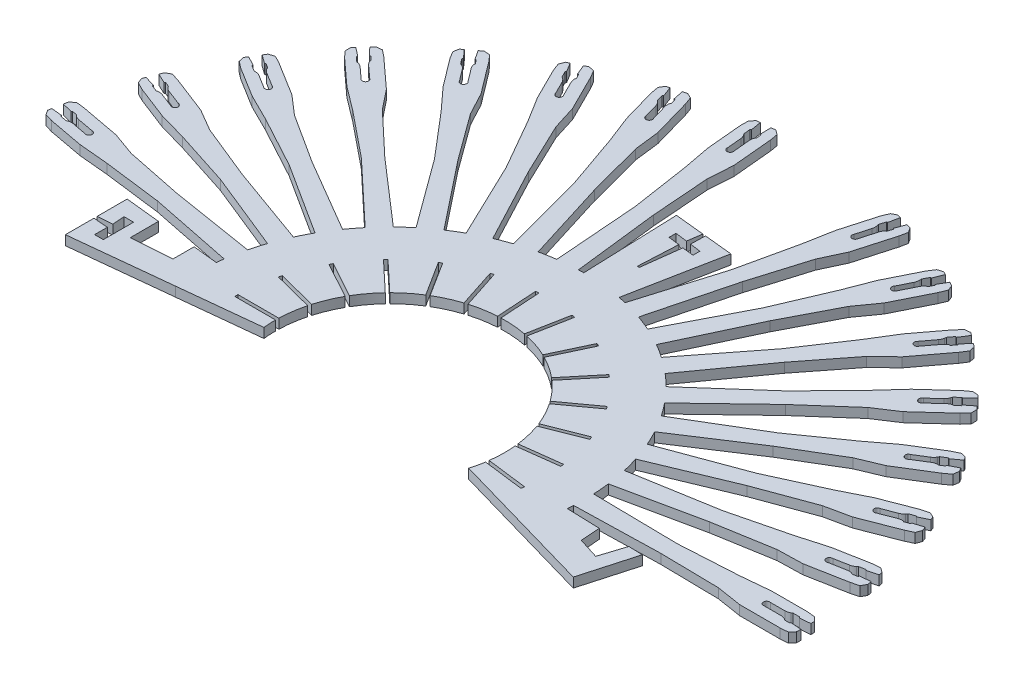
SolidWorks part; units mm, degrees
ref_plane "Front Plane" through (0, 0, 0) normal (0, 0, 1) x (1, 0, 0)
ref_plane "Top Plane" through (0, 0, 0) normal (0, 1, 0) x (1, 0, 0)
ref_plane "Right Plane" through (0, 0, 0) normal (1, 0, 0) x (0, 0, -1)
sketch "Sketch1" plane through (0, 0, 0) normal (0, 1, 0) x (1, 0, 0)
  line L5558 (72.849, 49.9) -> (72.743, 47.748) construction
  line L5559 (72.743, 47.748) -> (72.425, 45.667) construction
  line L5560 (72.425, 45.667) -> (71.896, 43.656) construction
  line L5561 (71.896, 43.656) -> (71.208, 41.716) construction
  line L5562 (71.208, 41.716) -> (70.309, 39.899) construction
  line L5563 (70.309, 39.899) -> (69.286, 38.171) construction
  line L5564 (69.286, 38.171) -> (66.71, 35.048) construction
  line L5565 (66.71, 35.048) -> (63.588, 32.491) construction
  line L5566 (63.588, 32.491) -> (61.877, 31.45) construction
  line L5567 (61.877, 31.45) -> (60.043, 30.551) construction
  line L5568 (60.043, 30.551) -> (58.12, 29.863) construction
  line L5569 (58.12, 29.863) -> (56.109, 29.333) construction
  line L5570 (56.109, 29.333) -> (54.01, 29.016) construction
  line L5571 (54.01, 29.016) -> (51.876, 28.91) construction
  line L5572 (51.876, 28.91) -> (49.724, 29.016) construction
  line L5573 (49.724, 29.016) -> (47.643, 29.333) construction
  line L5574 (47.643, 29.333) -> (45.632, 29.863) construction
  line L5575 (45.632, 29.863) -> (43.692, 30.551) construction
  line L5576 (43.692, 30.551) -> (41.839, 31.45) construction
  line L5577 (41.839, 31.45) -> (40.128, 32.491) construction
  line L5578 (40.128, 32.491) -> (37.006, 35.048) construction
  line L5579 (37.006, 35.048) -> (34.431, 38.171) construction
  line L5580 (34.431, 38.171) -> (33.408, 39.899) construction
  line L5581 (33.408, 39.899) -> (32.508, 41.716) construction
  line L5582 (32.508, 41.716) -> (31.821, 43.656) construction
  line L5583 (31.821, 43.656) -> (31.291, 45.667) construction
  line L5584 (31.291, 45.667) -> (30.974, 47.748) construction
  line L5585 (30.974, 47.748) -> (30.868, 49.9) construction
  line L5586 (30.868, 49.9) -> (30.974, 52.035) construction
  line L5587 (30.974, 52.035) -> (31.291, 54.134) construction
  line L5588 (31.291, 54.134) -> (31.821, 56.145) construction
  line L5589 (31.821, 56.145) -> (32.508, 58.067) construction
  line L5590 (32.508, 58.067) -> (33.408, 59.919) construction
  line L5591 (33.408, 59.919) -> (34.431, 61.648) construction
  line L5592 (34.431, 61.648) -> (37.006, 64.77) construction
  line L5593 (37.006, 64.77) -> (40.128, 67.328) construction
  line L5594 (40.128, 67.328) -> (41.839, 68.368) construction
  line L5595 (41.839, 68.368) -> (43.692, 69.268) construction
  line L5596 (43.692, 69.268) -> (45.632, 69.956) construction
  line L5597 (45.632, 69.956) -> (47.643, 70.485) construction
  line L5598 (47.643, 70.485) -> (49.724, 70.803) construction
  line L5599 (49.724, 70.803) -> (51.876, 70.908) construction
  line L5600 (51.876, 70.908) -> (54.01, 70.803) construction
  line L5601 (54.01, 70.803) -> (56.109, 70.485) construction
  line L5602 (56.109, 70.485) -> (58.12, 69.956) construction
  line L5603 (58.12, 69.956) -> (60.043, 69.268) construction
  line L5604 (60.043, 69.268) -> (61.877, 68.368) construction
  line L5605 (61.877, 68.368) -> (63.588, 67.328) construction
  line L5606 (63.588, 67.328) -> (66.71, 64.77) construction
  line L5607 (66.71, 64.77) -> (69.286, 61.648) construction
  line L5608 (69.286, 61.648) -> (70.309, 59.919) construction
  line L5609 (70.309, 59.919) -> (71.208, 58.067) construction
  line L5610 (71.208, 58.067) -> (71.896, 56.145) construction
  line L5611 (71.896, 56.145) -> (72.425, 54.134) construction
  line L5612 (72.425, 54.134) -> (72.743, 52.035) construction
  line L5613 (72.743, 52.035) -> (72.849, 49.9) construction
  line L5614 (62.054, 49.9) -> (61.842, 47.854) construction
  line L5615 (61.842, 47.854) -> (61.26, 45.932) construction
  line L5616 (61.26, 45.932) -> (60.307, 44.203) construction
  line L5617 (60.307, 44.203) -> (59.055, 42.704) construction
  line L5618 (59.055, 42.704) -> (57.556, 41.451) construction
  line L5619 (57.556, 41.451) -> (55.827, 40.499) construction
  line L5620 (55.827, 40.499) -> (53.922, 39.917) construction
  line L5621 (53.922, 39.917) -> (51.858, 39.705) construction
  line L5622 (51.858, 39.705) -> (49.795, 39.917) construction
  line L5623 (49.795, 39.917) -> (47.89, 40.499) construction
  line L5624 (47.89, 40.499) -> (46.143, 41.451) construction
  line L5625 (46.143, 41.451) -> (44.644, 42.704) construction
  line L5626 (44.644, 42.704) -> (43.392, 44.203) construction
  line L5627 (43.392, 44.203) -> (42.439, 45.932) construction
  line L5628 (42.439, 45.932) -> (41.857, 47.854) construction
  line L5629 (41.857, 47.854) -> (41.645, 49.9) construction
  line L5630 (41.645, 49.9) -> (41.857, 51.964) construction
  line L5631 (41.857, 51.964) -> (42.439, 53.869) construction
  line L5632 (42.439, 53.869) -> (43.392, 55.615) construction
  line L5633 (43.392, 55.615) -> (44.644, 57.115) construction
  line L5634 (44.644, 57.115) -> (46.143, 58.367) construction
  line L5635 (46.143, 58.367) -> (47.89, 59.32) construction
  line L5636 (47.89, 59.32) -> (49.795, 59.902) construction
  line L5637 (49.795, 59.902) -> (51.858, 60.113) construction
  line L5638 (51.858, 60.113) -> (53.922, 59.902) construction
  line L5639 (53.922, 59.902) -> (55.827, 59.32) construction
  line L5640 (55.827, 59.32) -> (57.556, 58.367) construction
  line L5641 (57.556, 58.367) -> (59.055, 57.115) construction
  line L5642 (59.055, 57.115) -> (60.307, 55.615) construction
  line L5643 (60.307, 55.615) -> (61.26, 53.869) construction
  line L5644 (61.26, 53.869) -> (61.842, 51.964) construction
  line L5645 (61.842, 51.964) -> (62.054, 49.9) construction
  line L5646 (30.85, 49.9) -> (51.841, 49.9) construction
  line L5647 (53.675, 70.82) -> (51.841, 49.9) construction
  line L5648 (72.531, 46.249) -> (51.858, 49.9) construction
  line L5649 (72.796, 48.436) -> (51.841, 49.9) construction
  line L5650 (51.488, 70.891) -> (51.841, 49.9) construction
  line L5651 (55.862, 70.52) -> (51.858, 49.9) construction
  line L5652 (30.956, 47.696) -> (51.841, 49.9) construction
  line L5653 (30.956, 52.088) -> (51.841, 49.9) construction
  line L5654 (72.037, 44.115) -> (51.841, 49.9) construction
  line L5655 (62.406, 49.177) -> (67.045, 49.424) construction
  line L5656 (67.345, 50.077) -> (67.469, 50.324) construction
  line L5657 (67.469, 50.324) -> (67.68, 50.377) construction
  line L5658 (67.68, 50.377) -> (67.892, 50.271) construction
  line L5659 (67.892, 50.271) -> (67.945, 50.059) construction
  line L5660 (67.945, 50.059) -> (67.839, 49.848) construction
  line L5661 (67.839, 49.848) -> (67.628, 49.759) construction
  line L5662 (67.628, 49.759) -> (67.416, 49.865) construction
  line L5663 (67.416, 49.865) -> (67.345, 50.077) construction
  line L5664 (69.832, 50.094) -> (69.938, 50.341) construction
  line L5665 (69.938, 50.341) -> (70.168, 50.394) construction
  line L5666 (70.168, 50.394) -> (70.379, 50.288) construction
  line L5667 (70.379, 50.288) -> (70.432, 50.077) construction
  line L5668 (70.432, 50.077) -> (70.326, 49.865) construction
  line L5669 (70.326, 49.865) -> (70.115, 49.777) construction
  line L5670 (70.115, 49.777) -> (69.903, 49.883) construction
  line L5671 (69.903, 49.883) -> (69.832, 50.094) construction
  line L5672 (67.045, 49.424) -> (71.702, 49.477) construction
  line L5673 (71.914, 50.094) -> (71.702, 49.477) construction
  line L5674 (62.389, 50.835) -> (67.045, 50.659) construction
  line L5675 (67.045, 50.659) -> (71.702, 50.712) construction
  line L5676 (71.914, 50.094) -> (71.702, 50.712) construction
  line L5677 (70.132, 50.377) -> (67.645, 50.359) construction
  line L5678 (70.15, 49.777) -> (67.645, 49.742) construction
  line L5679 (57.344, 49.953) -> (51.841, 49.9) construction
  line L5680 (62.353, 51.118) -> (66.887, 52.229) construction
  line L5681 (67.045, 52.917) -> (67.345, 53.252) construction
  line L5682 (67.345, 53.252) -> (67.557, 53.199) construction
  line L5683 (67.557, 53.199) -> (67.663, 52.987) construction
  line L5684 (67.663, 52.987) -> (67.61, 52.776) construction
  line L5685 (67.61, 52.776) -> (67.398, 52.652) construction
  line L5686 (67.398, 52.652) -> (67.187, 52.723) construction
  line L5687 (67.187, 52.723) -> (67.045, 52.917) construction
  line L5688 (69.48, 53.393) -> (69.779, 53.746) construction
  line L5689 (69.779, 53.746) -> (69.991, 53.693) construction
  line L5690 (69.991, 53.693) -> (70.097, 53.481) construction
  line L5691 (70.097, 53.481) -> (70.044, 53.269) construction
  line L5692 (70.044, 53.269) -> (69.832, 53.128) construction
  line L5693 (69.832, 53.128) -> (69.621, 53.217) construction
  line L5694 (69.621, 53.217) -> (69.48, 53.393) construction
  line L5695 (66.887, 52.229) -> (71.455, 53.128) construction
  line L5696 (71.543, 53.763) -> (71.455, 53.128) construction
  line L5697 (62.036, 52.758) -> (66.64, 53.428) construction
  line L5698 (66.64, 53.428) -> (71.208, 54.328) construction
  line L5699 (71.543, 53.781) -> (71.208, 54.328) construction
  line L5700 (69.744, 53.728) -> (67.292, 53.252) construction
  line L5701 (69.85, 53.128) -> (67.416, 52.634) construction
  line L5702 (57.238, 50.959) -> (51.841, 49.9) construction
  line L5703 (61.965, 53.023) -> (66.199, 54.945) construction
  line L5704 (66.234, 55.651) -> (66.446, 56.039) construction
  line L5705 (66.446, 56.039) -> (66.693, 56.021) construction
  line L5706 (66.693, 56.021) -> (66.851, 55.827) construction
  line L5707 (66.851, 55.827) -> (66.64, 55.457) construction
  line L5708 (66.64, 55.457) -> (66.393, 55.492) construction
  line L5709 (66.393, 55.492) -> (66.234, 55.651) construction
  line L5710 (68.545, 56.568) -> (68.756, 56.956) construction
  line L5711 (68.756, 56.956) -> (69.003, 56.938) construction
  line L5712 (69.003, 56.938) -> (69.162, 56.744) construction
  line L5713 (69.162, 56.744) -> (68.95, 56.374) construction
  line L5714 (68.95, 56.374) -> (68.703, 56.409) construction
  line L5715 (68.703, 56.409) -> (68.545, 56.568) construction
  line L5716 (66.199, 54.945) -> (70.52, 56.656) construction
  line L5717 (70.503, 57.309) -> (70.52, 56.656) construction
  line L5718 (61.348, 54.575) -> (65.74, 56.092) construction
  line L5719 (65.74, 56.092) -> (70.079, 57.803) construction
  line L5720 (70.503, 57.309) -> (70.079, 57.803) construction
  line L5721 (68.739, 56.938) -> (66.41, 56.021) construction
  line L5722 (68.968, 56.374) -> (66.64, 55.439) construction
  line L5723 (56.956, 51.929) -> (51.841, 49.9) construction
  line L5724 (61.225, 54.822) -> (65.035, 57.485) construction
  line L5725 (64.946, 58.191) -> (65.07, 58.614) construction
  line L5726 (65.07, 58.614) -> (65.317, 58.632) construction
  line L5727 (65.317, 58.632) -> (65.493, 58.473) construction
  line L5728 (65.493, 58.473) -> (65.528, 58.244) construction
  line L5729 (65.528, 58.244) -> (65.37, 58.05) construction
  line L5730 (65.37, 58.05) -> (64.946, 58.191) construction
  line L5731 (67.045, 59.514) -> (67.169, 59.937) construction
  line L5732 (67.169, 59.937) -> (67.416, 59.955) construction
  line L5733 (67.416, 59.955) -> (67.592, 59.796) construction
  line L5734 (67.592, 59.796) -> (67.628, 59.567) construction
  line L5735 (67.628, 59.567) -> (67.469, 59.373) construction
  line L5736 (67.469, 59.373) -> (67.045, 59.514) construction
  line L5737 (65.035, 57.485) -> (68.968, 59.972) construction
  line L5738 (68.827, 60.607) -> (68.968, 59.972) construction
  line L5739 (60.325, 56.233) -> (64.382, 58.526) construction
  line L5740 (64.382, 58.526) -> (68.315, 61.013) construction
  line L5741 (68.827, 60.607) -> (68.315, 61.013) construction
  line L5742 (67.169, 59.919) -> (65.052, 58.579) construction
  line L5743 (67.486, 59.39) -> (65.37, 58.067) construction
  line L5744 (56.497, 52.828) -> (51.858, 49.9) construction
  line L5745 (60.149, 56.444) -> (63.429, 59.761) construction
  line L5746 (63.2, 60.448) -> (63.147, 60.678) construction
  line L5747 (63.147, 60.678) -> (63.288, 60.889) construction
  line L5748 (63.288, 60.889) -> (63.5, 60.942) construction
  line L5749 (63.5, 60.942) -> (63.712, 60.837) construction
  line L5750 (63.712, 60.837) -> (63.765, 60.607) construction
  line L5751 (63.765, 60.607) -> (63.659, 60.396) construction
  line L5752 (63.659, 60.396) -> (63.412, 60.343) construction
  line L5753 (63.412, 60.343) -> (63.2, 60.448) construction
  line L5754 (65.017, 62.124) -> (64.964, 62.371) construction
  line L5755 (64.964, 62.371) -> (65.105, 62.583) construction
  line L5756 (65.105, 62.583) -> (65.317, 62.636) construction
  line L5757 (65.317, 62.636) -> (65.528, 62.53) construction
  line L5758 (65.528, 62.53) -> (65.581, 62.283) construction
  line L5759 (65.581, 62.283) -> (65.476, 62.071) construction
  line L5760 (65.476, 62.071) -> (65.229, 62.018) construction
  line L5761 (65.229, 62.018) -> (65.017, 62.124) construction
  line L5762 (63.429, 59.761) -> (66.834, 62.936) construction
  line L5763 (66.587, 63.535) -> (66.834, 62.936) construction
  line L5764 (59.02, 57.679) -> (62.583, 60.678) construction
  line L5765 (62.583, 60.678) -> (66.005, 63.835) construction
  line L5766 (66.587, 63.535) -> (66.005, 63.835) construction
  line L5767 (65.07, 62.548) -> (63.235, 60.854) construction
  line L5768 (65.493, 62.089) -> (63.659, 60.396) construction
  line L5769 (55.88, 53.622) -> (51.841, 49.9) construction
  line L5770 (58.808, 57.873) -> (61.419, 61.718) construction
  line L5771 (61.083, 62.353) -> (60.995, 62.583) construction
  line L5772 (60.995, 62.583) -> (61.083, 62.794) construction
  line L5773 (61.083, 62.794) -> (61.295, 62.9) construction
  line L5774 (61.295, 62.9) -> (61.507, 62.83) construction
  line L5775 (61.507, 62.83) -> (61.613, 62.618) construction
  line L5776 (61.613, 62.618) -> (61.524, 62.371) construction
  line L5777 (61.524, 62.371) -> (61.313, 62.301) construction
  line L5778 (61.313, 62.301) -> (61.083, 62.353) construction
  line L5779 (62.565, 64.329) -> (62.477, 64.576) construction
  line L5780 (62.477, 64.576) -> (62.565, 64.788) construction
  line L5781 (62.565, 64.788) -> (62.777, 64.893) construction
  line L5782 (62.777, 64.893) -> (62.988, 64.805) construction
  line L5783 (62.988, 64.805) -> (63.094, 64.594) construction
  line L5784 (63.094, 64.594) -> (63.006, 64.364) construction
  line L5785 (63.006, 64.364) -> (62.794, 64.276) construction
  line L5786 (62.794, 64.276) -> (62.565, 64.329) construction
  line L5787 (61.419, 61.718) -> (64.206, 65.458) construction
  line L5788 (63.835, 66.005) -> (64.206, 65.458) construction
  line L5789 (57.485, 58.861) -> (60.431, 62.459) construction
  line L5790 (60.431, 62.459) -> (63.2, 66.199) construction
  line L5791 (63.835, 66.005) -> (63.2, 66.199) construction
  line L5792 (62.53, 64.752) -> (61.031, 62.759) construction
  line L5793 (63.024, 64.382) -> (61.524, 62.389) construction
  line L5794 (55.122, 54.31) -> (51.858, 49.9) construction
  line L5795 (57.238, 59.002) -> (59.09, 63.271) construction
  line L5796 (58.649, 63.835) -> (58.508, 64.047) construction
  line L5797 (58.508, 64.047) -> (58.561, 64.258) construction
  line L5798 (58.561, 64.258) -> (58.755, 64.417) construction
  line L5799 (58.755, 64.417) -> (58.967, 64.364) construction
  line L5800 (58.967, 64.364) -> (59.126, 64.17) construction
  line L5801 (59.126, 64.17) -> (59.073, 63.941) construction
  line L5802 (59.073, 63.941) -> (58.879, 63.8) construction
  line L5803 (58.879, 63.8) -> (58.649, 63.835) construction
  line L5804 (59.743, 66.058) -> (59.602, 66.269) construction
  line L5805 (59.602, 66.269) -> (59.655, 66.481) construction
  line L5806 (59.655, 66.481) -> (59.849, 66.604) construction
  line L5807 (59.849, 66.604) -> (60.06, 66.587) construction
  line L5808 (60.06, 66.587) -> (60.219, 66.393) construction
  line L5809 (60.219, 66.393) -> (60.166, 66.163) construction
  line L5810 (60.166, 66.163) -> (59.972, 66.022) construction
  line L5811 (59.972, 66.022) -> (59.743, 66.058) construction
  line L5812 (59.09, 63.271) -> (61.136, 67.451) construction
  line L5813 (60.695, 67.927) -> (61.136, 67.451) construction
  line L5814 (55.739, 59.743) -> (57.979, 63.818) construction
  line L5815 (57.979, 63.818) -> (60.025, 67.998) construction
  line L5816 (60.678, 67.927) -> (60.025, 67.998) construction
  line L5817 (59.619, 66.463) -> (58.526, 64.223) construction
  line L5818 (60.184, 66.181) -> (59.073, 63.941) construction
  line L5819 (54.257, 54.822) -> (51.841, 49.9) construction
  line L5820 (55.457, 59.849) -> (56.497, 64.382) construction
  line L5821 (55.951, 64.841) -> (55.792, 64.999) construction
  line L5822 (55.792, 64.999) -> (55.792, 65.246) construction
  line L5823 (55.792, 65.246) -> (55.951, 65.423) construction
  line L5824 (55.951, 65.423) -> (56.18, 65.423) construction
  line L5825 (56.18, 65.423) -> (56.339, 65.264) construction
  line L5826 (56.339, 65.264) -> (56.339, 65.035) construction
  line L5827 (56.339, 65.035) -> (56.18, 64.876) construction
  line L5828 (56.18, 64.876) -> (55.951, 64.841) construction
  line L5829 (56.603, 67.239) -> (56.444, 67.398) construction
  line L5830 (56.444, 67.398) -> (56.444, 67.628) construction
  line L5831 (56.444, 67.628) -> (56.603, 67.822) construction
  line L5832 (56.603, 67.822) -> (56.85, 67.822) construction
  line L5833 (56.85, 67.822) -> (57.009, 67.663) construction
  line L5834 (57.009, 67.663) -> (57.009, 67.416) construction
  line L5835 (57.009, 67.416) -> (56.85, 67.257) construction
  line L5836 (56.85, 67.257) -> (56.603, 67.239) construction
  line L5837 (56.497, 64.382) -> (57.732, 68.88) construction
  line L5838 (57.203, 69.25) -> (57.732, 68.88) construction
  line L5839 (53.852, 60.29) -> (55.298, 64.717) construction
  line L5840 (55.298, 64.717) -> (56.533, 69.197) construction
  line L5841 (57.185, 69.25) -> (56.533, 69.197) construction
  line L5842 (56.427, 67.61) -> (55.757, 65.211) construction
  line L5843 (57.009, 67.451) -> (56.356, 65.035) construction
  line L5844 (53.305, 55.192) -> (51.841, 49.9) construction
  line L5845 (51.664, 60.484) -> (50.994, 65.088) construction
  line L5846 (50.324, 65.317) -> (50.112, 65.423) construction
  line L5847 (50.112, 65.423) -> (50.024, 65.634) construction
  line L5848 (50.024, 65.634) -> (50.112, 65.846) construction
  line L5849 (50.112, 65.846) -> (50.324, 65.952) construction
  line L5850 (50.324, 65.952) -> (50.553, 65.846) construction
  line L5851 (50.553, 65.846) -> (50.641, 65.634) construction
  line L5852 (50.641, 65.634) -> (50.553, 65.423) construction
  line L5853 (50.553, 65.423) -> (50.324, 65.317) construction
  line L5854 (50.077, 67.786) -> (49.865, 67.892) construction
  line L5855 (49.865, 67.892) -> (49.795, 68.104) construction
  line L5856 (49.795, 68.104) -> (49.865, 68.315) construction
  line L5857 (49.865, 68.315) -> (50.077, 68.421) construction
  line L5858 (50.077, 68.421) -> (50.324, 68.315) construction
  line L5859 (50.324, 68.315) -> (50.394, 68.104) construction
  line L5860 (50.394, 68.104) -> (50.324, 67.892) construction
  line L5861 (50.324, 67.892) -> (50.077, 67.786) construction
  line L5862 (50.994, 65.088) -> (50.535, 69.727) construction
  line L5863 (49.918, 69.885) -> (50.535, 69.727) construction
  line L5864 (50.006, 60.325) -> (49.759, 64.964) construction
  line L5865 (49.759, 64.964) -> (49.318, 69.603) construction
  line L5866 (49.9, 69.885) -> (49.318, 69.603) construction
  line L5867 (49.777, 68.068) -> (50.024, 65.599) construction
  line L5868 (50.377, 68.139) -> (50.624, 65.652) construction
  line L5869 (51.312, 55.368) -> (51.858, 49.9) construction
  line L5870 (49.724, 60.272) -> (48.225, 64.664) construction
  line L5871 (47.519, 64.788) -> (47.308, 64.841) construction
  line L5872 (47.308, 64.841) -> (47.184, 65.052) construction
  line L5873 (47.184, 65.052) -> (47.237, 65.264) construction
  line L5874 (47.237, 65.264) -> (47.413, 65.387) construction
  line L5875 (47.413, 65.387) -> (47.66, 65.334) construction
  line L5876 (47.66, 65.334) -> (47.784, 65.158) construction
  line L5877 (47.784, 65.158) -> (47.731, 64.946) construction
  line L5878 (47.731, 64.946) -> (47.519, 64.788) construction
  line L5879 (46.831, 67.169) -> (46.62, 67.222) construction
  line L5880 (46.62, 67.222) -> (46.496, 67.433) construction
  line L5881 (46.496, 67.433) -> (46.549, 67.645) construction
  line L5882 (46.549, 67.645) -> (46.725, 67.769) construction
  line L5883 (46.725, 67.769) -> (46.972, 67.716) construction
  line L5884 (46.972, 67.716) -> (47.096, 67.539) construction
  line L5885 (47.096, 67.539) -> (47.043, 67.328) construction
  line L5886 (47.043, 67.328) -> (46.831, 67.169) construction
  line L5887 (48.225, 64.664) -> (46.937, 69.144) construction
  line L5888 (46.284, 69.18) -> (46.937, 69.144) construction
  line L5889 (48.119, 59.796) -> (47.043, 64.329) construction
  line L5890 (47.043, 64.329) -> (45.738, 68.809) construction
  line L5891 (46.267, 69.18) -> (45.738, 68.792) construction
  line L5892 (46.478, 67.381) -> (47.166, 64.982) construction
  line L5893 (47.061, 67.557) -> (47.766, 65.158) construction
  line L5894 (50.324, 55.174) -> (51.841, 49.9) construction
  line L5895 (47.854, 59.708) -> (45.579, 63.747) construction
  line L5896 (44.873, 63.729) -> (44.662, 63.765) construction
  line L5897 (44.662, 63.765) -> (44.503, 63.923) construction
  line L5898 (44.503, 63.923) -> (44.503, 64.153) construction
  line L5899 (44.503, 64.153) -> (44.662, 64.311) construction
  line L5900 (44.662, 64.311) -> (44.891, 64.311) construction
  line L5901 (44.891, 64.311) -> (45.05, 64.135) construction
  line L5902 (45.05, 64.135) -> (45.05, 63.923) construction
  line L5903 (45.05, 63.923) -> (44.873, 63.729) construction
  line L5904 (43.762, 65.952) -> (43.55, 65.969) construction
  line L5905 (43.55, 65.969) -> (43.356, 66.128) construction
  line L5906 (43.356, 66.128) -> (43.392, 66.375) construction
  line L5907 (43.392, 66.375) -> (43.55, 66.534) construction
  line L5908 (43.55, 66.534) -> (43.78, 66.534) construction
  line L5909 (43.78, 66.534) -> (43.938, 66.34) construction
  line L5910 (43.938, 66.34) -> (43.938, 66.128) construction
  line L5911 (43.938, 66.128) -> (43.762, 65.952) construction
  line L5912 (45.579, 63.747) -> (43.498, 67.91) construction
  line L5913 (42.845, 67.839) -> (43.498, 67.91) construction
  line L5914 (46.373, 58.949) -> (44.485, 63.2) construction
  line L5915 (44.485, 63.2) -> (42.386, 67.363) construction
  line L5916 (42.827, 67.839) -> (42.386, 67.363) construction
  line L5917 (43.374, 66.111) -> (44.485, 63.87) construction
  line L5918 (43.921, 66.393) -> (45.032, 64.153) construction
  line L5919 (49.389, 54.804) -> (51.841, 49.9) construction
  line L5920 (46.126, 58.808) -> (43.145, 62.371) construction
  line L5921 (42.457, 62.23) -> (42.245, 62.195) construction
  line L5922 (42.245, 62.195) -> (42.051, 62.336) construction
  line L5923 (42.051, 62.336) -> (41.998, 62.565) construction
  line L5924 (41.998, 62.565) -> (42.139, 62.759) construction
  line L5925 (42.139, 62.759) -> (42.369, 62.777) construction
  line L5926 (42.369, 62.777) -> (42.563, 62.653) construction
  line L5927 (42.563, 62.653) -> (42.58, 62.442) construction
  line L5928 (42.58, 62.442) -> (42.457, 62.23) construction
  line L5929 (40.958, 64.188) -> (40.746, 64.17) construction
  line L5930 (40.746, 64.17) -> (40.552, 64.294) construction
  line L5931 (40.552, 64.294) -> (40.499, 64.541) construction
  line L5932 (40.499, 64.541) -> (40.64, 64.717) construction
  line L5933 (40.64, 64.717) -> (40.869, 64.752) construction
  line L5934 (40.869, 64.752) -> (41.063, 64.611) construction
  line L5935 (41.063, 64.611) -> (41.081, 64.4) construction
  line L5936 (41.081, 64.4) -> (40.958, 64.188) construction
  line L5937 (43.145, 62.371) -> (40.323, 66.075) construction
  line L5938 (39.705, 65.881) -> (40.323, 66.075) construction
  line L5939 (44.803, 57.803) -> (42.157, 61.63) construction
  line L5940 (42.157, 61.63) -> (39.352, 65.334) construction
  line L5941 (39.705, 65.881) -> (39.352, 65.334) construction
  line L5942 (40.534, 64.276) -> (42.051, 62.301) construction
  line L5943 (41.028, 64.647) -> (42.545, 62.671) construction
  line L5944 (48.525, 54.275) -> (51.858, 49.9) construction
  line L5945 (44.591, 57.609) -> (41.01, 60.572) construction
  line L5946 (40.358, 60.29) -> (40.146, 60.219) construction
  line L5947 (40.146, 60.219) -> (39.934, 60.325) construction
  line L5948 (39.934, 60.325) -> (39.846, 60.537) construction
  line L5949 (39.846, 60.537) -> (39.952, 60.748) construction
  line L5950 (39.952, 60.748) -> (40.164, 60.819) construction
  line L5951 (40.164, 60.819) -> (40.375, 60.748) construction
  line L5952 (40.375, 60.748) -> (40.464, 60.537) construction
  line L5953 (40.464, 60.537) -> (40.358, 60.29) construction
  line L5954 (38.523, 61.965) -> (38.312, 61.877) construction
  line L5955 (38.312, 61.877) -> (38.1, 61.983) construction
  line L5956 (38.1, 61.983) -> (38.012, 62.195) construction
  line L5957 (38.012, 62.195) -> (38.118, 62.406) construction
  line L5958 (38.118, 62.406) -> (38.329, 62.495) construction
  line L5959 (38.329, 62.495) -> (38.541, 62.406) construction
  line L5960 (38.541, 62.406) -> (38.629, 62.195) construction
  line L5961 (38.629, 62.195) -> (38.523, 61.965) construction
  line L5962 (41.01, 60.572) -> (37.553, 63.694) construction
  line L5963 (36.989, 63.394) -> (37.553, 63.694) construction
  line L5964 (43.48, 56.374) -> (40.181, 59.655) construction
  line L5965 (40.181, 59.655) -> (36.724, 62.777) construction
  line L5966 (36.971, 63.377) -> (36.724, 62.777) construction
  line L5967 (38.1, 61.965) -> (39.952, 60.29) construction
  line L5968 (38.506, 62.424) -> (40.358, 60.748) construction
  line L5969 (47.784, 53.587) -> (51.841, 49.9) construction
  line L5970 (43.303, 56.145) -> (39.247, 58.402) construction
  line L5971 (38.647, 58.014) -> (38.453, 57.908) construction
  line L5972 (38.453, 57.908) -> (38.223, 57.961) construction
  line L5973 (38.223, 57.961) -> (38.118, 58.173) construction
  line L5974 (38.118, 58.173) -> (38.171, 58.385) construction
  line L5975 (38.171, 58.385) -> (38.594, 58.455) construction
  line L5976 (38.594, 58.455) -> (38.7, 58.244) construction
  line L5977 (38.7, 58.244) -> (38.647, 58.014) construction
  line L5978 (36.53, 59.32) -> (36.354, 59.214) construction
  line L5979 (36.354, 59.214) -> (36.107, 59.267) construction
  line L5980 (36.107, 59.267) -> (36.001, 59.478) construction
  line L5981 (36.001, 59.478) -> (36.054, 59.69) construction
  line L5982 (36.054, 59.69) -> (36.477, 59.761) construction
  line L5983 (36.477, 59.761) -> (36.583, 59.549) construction
  line L5984 (36.583, 59.549) -> (36.53, 59.32) construction
  line L5985 (39.247, 58.402) -> (35.278, 60.854) construction
  line L5986 (34.766, 60.448) -> (35.278, 60.837) construction
  line L5987 (42.439, 54.733) -> (38.594, 57.344) construction
  line L5988 (38.594, 57.344) -> (34.625, 59.796) construction
  line L5989 (34.766, 60.431) -> (34.625, 59.796) construction
  line L5990 (36.124, 59.249) -> (38.241, 57.926) construction
  line L5991 (36.442, 59.761) -> (38.559, 58.455) construction
  line L5992 (47.184, 52.776) -> (51.841, 49.9) construction
  line L5993 (42.316, 54.469) -> (37.888, 55.951) construction
  line L5994 (37.377, 55.457) -> (37.218, 55.316) construction
  line L5995 (37.218, 55.316) -> (36.989, 55.316) construction
  line L5996 (36.989, 55.316) -> (36.83, 55.51) construction
  line L5997 (36.83, 55.51) -> (36.848, 55.739) construction
  line L5998 (36.848, 55.739) -> (37.006, 55.898) construction
  line L5999 (37.006, 55.898) -> (37.253, 55.88) construction
  line L6000 (37.253, 55.88) -> (37.412, 55.686) construction
  line L6001 (37.412, 55.686) -> (37.377, 55.457) construction
  line L6002 (35.066, 56.356) -> (34.907, 56.215) construction
  line L6003 (34.907, 56.215) -> (34.678, 56.215) construction
  line L6004 (34.678, 56.215) -> (34.519, 56.409) construction
  line L6005 (34.519, 56.409) -> (34.537, 56.638) construction
  line L6006 (34.537, 56.638) -> (34.696, 56.797) construction
  line L6007 (34.696, 56.797) -> (34.943, 56.78) construction
  line L6008 (34.943, 56.78) -> (35.101, 56.586) construction
  line L6009 (35.101, 56.586) -> (35.066, 56.356) construction
  line L6010 (37.888, 55.951) -> (33.549, 57.626) construction
  line L6011 (33.126, 57.132) -> (33.549, 57.626) construction
  line L6012 (41.716, 52.917) -> (37.447, 54.804) construction
  line L6013 (37.447, 54.804) -> (33.108, 56.48) construction
  line L6014 (33.126, 57.132) -> (33.108, 56.48) construction
  line L6015 (34.678, 56.198) -> (37.006, 55.298) construction
  line L6016 (34.89, 56.78) -> (37.218, 55.88) construction
  line L6017 (46.725, 51.876) -> (51.858, 49.9) construction
  line L6018 (41.628, 52.652) -> (37.024, 53.287) construction
  line L6019 (36.601, 52.705) -> (36.477, 52.529) construction
  line L6020 (36.477, 52.529) -> (36.23, 52.493) construction
  line L6021 (36.23, 52.493) -> (36.054, 52.652) construction
  line L6022 (36.054, 52.652) -> (36.019, 52.899) construction
  line L6023 (36.019, 52.899) -> (36.389, 53.111) construction
  line L6024 (36.389, 53.111) -> (36.583, 52.952) construction
  line L6025 (36.583, 52.952) -> (36.601, 52.705) construction
  line L6026 (34.167, 53.164) -> (34.043, 52.987) construction
  line L6027 (34.043, 52.987) -> (33.796, 52.952) construction
  line L6028 (33.796, 52.952) -> (33.62, 53.111) construction
  line L6029 (33.62, 53.111) -> (33.584, 53.358) construction
  line L6030 (33.584, 53.358) -> (33.955, 53.569) construction
  line L6031 (33.955, 53.569) -> (34.149, 53.411) construction
  line L6032 (34.149, 53.411) -> (34.167, 53.164) construction
  line L6033 (37.024, 53.287) -> (32.438, 54.134) construction
  line L6034 (32.12, 53.587) -> (32.438, 54.134) construction
  line L6035 (41.328, 51.012) -> (36.795, 52.07) construction
  line L6036 (36.795, 52.07) -> (32.226, 52.934) construction
  line L6037 (32.12, 53.569) -> (32.226, 52.934) construction
  line L6038 (33.814, 52.952) -> (36.266, 52.493) construction
  line L6039 (33.92, 53.552) -> (36.371, 53.093) construction
  line L6040 (46.461, 50.906) -> (51.858, 49.9) construction
  line L6041 (57.856, 49.9) -> (57.714, 48.683) construction
  line L6042 (57.714, 48.683) -> (57.379, 47.572) construction
  line L6043 (57.379, 47.572) -> (56.815, 46.567) construction
  line L6044 (56.815, 46.567) -> (56.109, 45.667) construction
  line L6045 (56.109, 45.667) -> (55.21, 44.944) construction
  line L6046 (55.21, 44.944) -> (54.204, 44.397) construction
  line L6047 (54.204, 44.397) -> (53.093, 44.044) construction
  line L6048 (53.093, 44.044) -> (51.876, 43.921) construction
  line L6049 (51.876, 43.921) -> (50.659, 44.044) construction
  line L6050 (50.659, 44.044) -> (49.512, 44.397) construction
  line L6051 (49.512, 44.397) -> (48.507, 44.944) construction
  line L6052 (48.507, 44.944) -> (47.607, 45.667) construction
  line L6053 (47.607, 45.667) -> (46.902, 46.567) construction
  line L6054 (46.902, 46.567) -> (46.337, 47.572) construction
  line L6055 (46.337, 47.572) -> (46.002, 48.683) construction
  line L6056 (46.002, 48.683) -> (45.861, 49.9) construction
  line L6057 (45.861, 49.9) -> (46.002, 51.118) construction
  line L6058 (46.002, 51.118) -> (46.337, 52.246) construction
  line L6059 (46.337, 52.246) -> (46.902, 53.252) construction
  line L6060 (46.902, 53.252) -> (47.607, 54.151) construction
  line L6061 (47.607, 54.151) -> (48.507, 54.875) construction
  line L6062 (48.507, 54.875) -> (49.512, 55.421) construction
  line L6063 (49.512, 55.421) -> (50.659, 55.774) construction
  line L6064 (50.659, 55.774) -> (51.876, 55.898) construction
  line L6065 (51.876, 55.898) -> (53.093, 55.774) construction
  line L6066 (53.093, 55.774) -> (54.204, 55.421) construction
  line L6067 (54.204, 55.421) -> (55.21, 54.875) construction
  line L6068 (55.21, 54.875) -> (56.109, 54.151) construction
  line L6069 (56.109, 54.151) -> (56.815, 53.252) construction
  line L6070 (56.815, 53.252) -> (57.379, 52.246) construction
  line L6071 (57.379, 52.246) -> (57.714, 51.118) construction
  line L6072 (57.714, 51.118) -> (57.856, 49.9) construction
sketch "Sketch2" plane through (0, 0, 0) normal (0, 1, 0) x (1, 0, 0)
  line L0 (41.7366, 50.9583) -> (36.5552, 51.5014)
  line L1 (51.841, 49.9) -> (53.163, 64.9033) construction
  line L2 (30.956, 52.088) -> (51.841, 49.9) construction
  line L3 (36.5552, 51.5014) -> (36.5552, 48.2869)
  line L4 (30.956, 47.696) -> (51.841, 49.9) construction
  line L5 (36.5552, 48.2869) -> (41.7327, 48.8337)
  line L7 (61.6124, 47.1011) -> (66.5007, 45.7008)
  line L8 (72.037, 44.115) -> (51.841, 49.9) construction
  line L9 (66.5007, 45.7008) -> (67.012, 48.8401)
  line L10 (72.796, 48.436) -> (51.841, 49.9) construction
  line L11 (67.012, 48.8401) -> (61.9609, 49.0012)
  line L12 (62.054, 49.9) -> (61.842, 47.854) construction
  line L13 (51.765, 60.0594) -> (51.586, 65.0642)
  line L14 (51.488, 70.891) -> (51.841, 49.9) construction
  line L15 (51.586, 65.0642) -> (54.7401, 64.7424)
  line L16 (55.862, 70.52) -> (51.858, 49.9) construction
  line L17 (54.7401, 64.7424) -> (53.794, 59.8702)
  circle A0 centre (51.841, 49.9) radius 5.9707
  arc A1 (61.9609, 49.0012) -> (53.794, 59.8702) centre (51.841, 49.9) ccw
  arc A2 (41.7375, 50.967) -> (41.7366, 50.9583) centre (51.841, 49.9) ccw
  arc A3 (41.7327, 48.8337) -> (41.7338, 48.8238) centre (51.841, 49.9) ccw
  arc A4 (41.7338, 48.8238) -> (61.6124, 47.1011) centre (51.841, 49.9) ccw
  arc A5 (51.765, 60.0594) -> (41.7375, 50.967) centre (51.841, 49.9) ccw
extrude "Boss-Extrude1" add sketch "Sketch2" along normal blind 0.5
sketch "Sketch3" plane through (0, 0, 0) normal (0, 1, 0) x (1, 0, 0)
  line L0 (34.2118, 50.4323) -> (32.9093, 50.6404)
  line L1 (30.85, 49.9) -> (51.841, 49.9) construction
  line L2 (41.7282, 50.4911) -> (37.2554, 50.3818)
  line L3 (32.9093, 50.6404) -> (30.8099, 50.6404)
  line L4 (30.8099, 50.6404) -> (30.3951, 50.6098)
  line L5 (30.3951, 50.6098) -> (30.1967, 50.3818)
  line L6 (32.1942, 50.0581) -> (31.3331, 50.0581)
  line L7 (37.2554, 50.3818) -> (34.2118, 50.4323)
  line L8 (31.0996, 50.116) -> (31.0522, 50.1661)
  line L9 (30.7793, 50.1661) -> (31.0522, 50.1661)
  line L10 (32.1963, 49.7413) -> (31.4424, 49.7413)
  line L11 (41.7282, 50.4911) -> (41.7282, 49.4512)
  line L12 (31.194, 49.6753) -> (31.1199, 49.6329)
  line L13 (30.7793, 50.1661) -> (30.7516, 50.116)
  line L14 (30.7516, 50.116) -> (30.1967, 50.1553)
  line L15 (30.7788, 49.6329) -> (31.1199, 49.6329)
  line L16 (30.1967, 50.1553) -> (30.1967, 50.3818)
  line L17 (30.3951, 49.2413) -> (30.1967, 49.4512)
  line L18 (30.8191, 49.1966) -> (30.3951, 49.2413)
  line L19 (32.6688, 49.1966) -> (30.8191, 49.1966)
  line L20 (41.7282, 49.4512) -> (37.2554, 49.5186)
  line L21 (34.213, 49.341) -> (32.6688, 49.1966)
  line L22 (30.7788, 49.6329) -> (30.7516, 49.685)
  line L23 (30.7516, 49.685) -> (30.1967, 49.6405)
  line L24 (30.1967, 49.6405) -> (30.1967, 49.4512)
  line L25 (37.2554, 49.5186) -> (34.213, 49.341)
  line L26 (51.841, 49.9) -> (28.9127, 49.9) construction
  circle A0 centre (32.2385, 49.7358) radius 0.1651 construction
  circle A1 centre (30.7793, 50.1661) radius 0.1651 construction
  circle A3 centre (32.2385, 50.0642) radius 0.1651 construction
  circle A4 centre (29.8485, 50.8372) radius 0.1651 construction
  arc A5 (31.3331, 50.0581) -> (31.0996, 50.116) centre (31.3331, 50.5581) cw
  arc A6 (32.1963, 49.7413) -> (32.1942, 50.0581) centre (32.2385, 49.9) ccw
  arc A7 (31.4424, 49.7413) -> (31.194, 49.6753) centre (31.4424, 49.2413) ccw
  circle A8 centre (32.2385, 50.3818) radius 0.1651 construction
  point P21 (41.7282, 49.9)
  point P54 (41.7282, 49.9)
  dimension "D1" = 0.5
extrude "Boss-Extrude2" add sketch "Sketch3" along normal blind 0.5
sketch "Sketch5" plane through (0, 0, 0) normal (0, 1, 0) x (1, 0, 0)
  line L0 (51.841, 49.9) -> (51.841, 47.986)
  line L1 (30.85, 49.9) -> (51.841, 49.9) construction
  line L2 (51.841, 49.9) -> (47.5187, 49.9)
  line L4 (47.5187, 49.9) -> (51.841, 47.986)
extrude "Boss-Extrude3" add sketch "Sketch5" along normal blind 0.5 separate body
pattern_circular "CirPattern1" count 18 over 180 about axis through (51.841, 0.5, -49.9) along (0, -1, 0) of "Boss-Extrude2"
sketch "Sketch8" plane through (0, 0, 0) normal (0, 1, 0) x (1, 0, 0)
  line L0 (36.5552, 48.2869) -> (27.9956, 47.1697)
  line L1 (27.9956, 47.1697) -> (27.9956, 52.8907)
  line L2 (27.9956, 52.8907) -> (36.5552, 51.5014)
  line L3 (36.5552, 51.5014) -> (36.5552, 48.754)
  line L5 (36.5552, 48.754) -> (36.5552, 48.2869)
  line L6 (51.6556, 72.5266) -> (51.586, 65.0642)
  line L7 (51.586, 65.0642) -> (54.7401, 64.7424)
  line L8 (54.7401, 64.7424) -> (56.407, 72.5266)
  line L9 (56.407, 72.5266) -> (51.6556, 72.5266)
  line L10 (47.955, 51.5014) -> (46.9983, 48.798)
  line L11 (46.9983, 48.798) -> (52.8392, 46.1614)
  line L12 (52.8392, 46.1614) -> (54.7401, 51.7191)
  line L13 (56.497, 52.828) -> (51.858, 49.9) construction
  line L14 (54.7401, 51.7191) -> (47.955, 51.5014)
extrude "Cut-Extrude4" cut sketch "Sketch8" against normal blind 0.5 and the other way through all
sketch "Sketch9" plane through (0, 0, 0) normal (0, 1, 0) x (1, 0, 0)
  line L0 (36.5552, 48.2869) -> (47.0091, 49.3901)
  line L1 (51.841, 49.9) -> (66.5007, 45.7008)
  line L2 (66.5007, 45.7008) -> (51.841, 34.8579)
  line L3 (51.841, 34.8579) -> (36.5552, 48.2869)
  line L4 (47.0091, 49.3901) -> (47.588, 50.4909)
  line L5 (47.588, 50.4909) -> (51.841, 49.9)
extrude "Cut-Extrude6" cut sketch "Sketch9" against normal blind 0.5 and the other way through all
sketch "Sketch12" plane through (0, 0, 0) normal (0, 1, 0) x (1, 0, 0)
  line L0 (36.5552, 51.5014) -> (38.3774, 51.5014)
  line L1 (38.3774, 51.5014) -> (38.3774, 49.8464)
  line L2 (38.3774, 49.8464) -> (40.4501, 49.9851)
  line L3 (40.4501, 49.9851) -> (40.4501, 51.1692)
  line L4 (40.4501, 51.1692) -> (37.3172, 51.7206)
  line L5 (37.3172, 51.7206) -> (36.5552, 51.5014)
  line L6 (66.0368, 49.0067) -> (65.0952, 45.6712)
  line L7 (53.2955, 66.1067) -> (53.0083, 64.1642)
  line L8 (67.012, 48.8401) -> (61.9609, 49.0012) construction
  line L9 (65.2739, 48.8955) -> (64.8588, 47.5883)
  line L10 (64.8588, 47.5883) -> (63.7611, 47.9369)
  line L11 (63.7611, 47.9369) -> (63.678, 49.0649)
  line L12 (63.678, 49.0649) -> (65.5048, 49.0067)
  line L13 (65.5048, 49.0067) -> (65.2739, 48.8955)
  line L14 (65.0952, 45.6712) -> (66.9581, 45.1452)
  line L15 (35.4312, 49.8586) -> (37.3125, 49.9972)
  line L16 (37.3125, 49.9972) -> (37.2663, 50.6247)
  line L17 (37.2663, 50.6247) -> (37.7661, 50.6247)
  line L18 (37.7661, 50.6247) -> (37.7661, 49.0512)
  line L19 (37.7661, 49.0512) -> (37.3125, 49.0512)
  line L20 (37.3125, 49.0512) -> (37.3125, 49.7158)
  line L21 (37.3125, 49.7158) -> (35.4312, 49.8586)
  line L22 (66.9581, 45.1452) -> (67.4623, 48.8914)
  line L23 (67.4623, 48.8914) -> (66.0368, 49.0067)
  line L24 (53.0083, 64.1642) -> (52.3858, 64.243)
  line L25 (52.3858, 64.243) -> (52.3858, 63.8789)
  line L26 (52.3858, 63.8789) -> (52.9684, 63.8051)
  line L27 (53.8144, 63.698) -> (53.8144, 64.0546)
  line L28 (53.8144, 64.0546) -> (53.253, 64.1319)
  line L29 (53.253, 64.1319) -> (53.2955, 66.1067)
  line L30 (52.9684, 63.8051) -> (52.8651, 61.7504)
  line L31 (53.22, 63.7596) -> (53.8144, 63.698)
  line L32 (52.8651, 61.7504) -> (52.9684, 61.7443)
  line L33 (52.9684, 61.7443) -> (53.22, 63.7596)
  line L34 (51.841, 49.9) -> (53.5625, 69.0822) construction
  circle A0 centre (0, 0) radius 0.1651 construction
  circle A1 centre (52.4536, 66.1109) radius 0.1651 construction
extrude "Cut-Extrude13" cut sketch "Sketch12" along normal blind 10
sketch "Sketch13" plane through (0, 0, 0) normal (0, 1, 0) x (1, 0, 0)
  line L0 (49.3919, 50.5414) -> (44.0052, 51.9244)
  line L1 (49.3092, 49.9121) -> (43.7478, 49.9121)
  line L2 (49.3092, 49.9121) -> (49.3092, 50.078)
  line L3 (49.3092, 50.078) -> (43.7478, 50.078)
  line L4 (43.7478, 49.9121) -> (43.7478, 50.078)
  line L5 (49.3919, 50.5414) -> (49.4332, 50.702)
  line L6 (49.4332, 50.702) -> (44.0465, 52.0851)
  line L7 (44.0052, 51.9244) -> (44.0465, 52.0851)
  line L8 (49.6285, 51.1303) -> (44.755, 53.8095)
  line L9 (49.6285, 51.1303) -> (49.7084, 51.2756)
  line L10 (49.7084, 51.2756) -> (44.8349, 53.9549)
  line L11 (44.755, 53.8095) -> (44.8349, 53.9549)
  line L12 (50.0042, 51.6418) -> (45.9501, 55.4489)
  line L13 (50.0042, 51.6418) -> (50.1177, 51.7628)
  line L14 (50.1177, 51.7628) -> (46.0636, 55.5698)
  line L15 (45.9501, 55.4489) -> (46.0636, 55.5698)
  line L16 (50.4952, 52.0439) -> (47.5153, 56.7396)
  line L17 (50.4952, 52.0439) -> (50.6353, 52.1328)
  line L18 (50.6353, 52.1328) -> (47.6553, 56.8285)
  line L19 (47.5153, 56.7396) -> (47.6553, 56.8285)
  line L20 (51.0708, 52.3113) -> (49.3523, 57.6005)
  line L21 (51.0708, 52.3113) -> (51.2286, 52.3625)
  line L22 (51.2286, 52.3625) -> (49.51, 57.6517)
  line L23 (49.3523, 57.6005) -> (49.51, 57.6517)
  line L24 (51.6949, 52.427) -> (51.3457, 57.9775)
  line L25 (51.6949, 52.427) -> (51.8604, 52.4375)
  line L26 (51.8604, 52.4375) -> (51.5112, 57.9879)
  line L27 (51.3457, 57.9775) -> (51.5112, 57.9879)
  line L28 (52.3281, 52.384) -> (53.3702, 57.8469)
  line L29 (52.3281, 52.384) -> (52.491, 52.3529)
  line L30 (52.491, 52.3529) -> (53.5331, 57.8158)
  line L31 (53.3702, 57.8469) -> (53.5331, 57.8158)
  line L32 (52.9307, 52.1848) -> (55.2986, 57.217)
  line L33 (52.9307, 52.1848) -> (53.0808, 52.1142)
  line L34 (53.0808, 52.1142) -> (55.4487, 57.1463)
  line L35 (55.2986, 57.217) -> (55.4487, 57.1463)
  line L36 (53.4648, 51.8421) -> (57.0098, 56.1272)
  line L37 (53.4648, 51.8421) -> (53.5926, 51.7363)
  line L38 (53.5926, 51.7363) -> (57.1376, 56.0215)
  line L39 (57.0098, 56.1272) -> (57.1376, 56.0215)
  line L40 (53.897, 51.3772) -> (58.3962, 54.6461)
  line L41 (53.897, 51.3772) -> (53.9945, 51.243)
  line L42 (53.9945, 51.243) -> (58.4937, 54.5119)
  line L43 (58.3962, 54.6461) -> (58.4937, 54.5119)
  line L44 (54.1999, 50.8195) -> (59.3708, 52.8668)
  line L45 (54.1999, 50.8195) -> (54.261, 50.6653)
  line L46 (54.261, 50.6653) -> (59.4318, 52.7126)
  line L47 (59.3708, 52.8668) -> (59.4318, 52.7126)
  line L48 (54.3546, 50.204) -> (59.8722, 50.901)
  line L49 (54.3546, 50.204) -> (54.3754, 50.0394)
  line L50 (54.3754, 50.0394) -> (59.893, 50.7365)
  line L51 (59.8722, 50.901) -> (59.893, 50.7365)
  line L52 (54.3514, 49.5693) -> (59.869, 48.8723)
  line L53 (54.3514, 49.5693) -> (54.3307, 49.4048)
  line L54 (54.3307, 49.4048) -> (59.8482, 48.7077)
  line L55 (59.869, 48.8723) -> (59.8482, 48.7077)
  line L56 (54.1905, 48.9554) -> (59.3614, 46.9081)
  line L57 (54.1905, 48.9554) -> (54.1294, 48.8012)
  line L58 (54.1294, 48.8012) -> (59.3003, 46.7539)
  line L59 (59.3614, 46.9081) -> (59.3003, 46.7539)
  line L60 (53.882, 48.4008) -> (58.3812, 45.1319)
  line L61 (53.882, 48.4008) -> (53.7845, 48.2666)
  line L62 (53.7845, 48.2666) -> (58.2837, 44.9977)
  line L63 (58.3812, 45.1319) -> (58.2837, 44.9977)
  line L64 (53.4452, 47.9403) -> (56.9901, 43.6552)
  line L65 (53.4452, 47.9403) -> (53.3174, 47.8346)
  line L66 (53.3174, 47.8346) -> (56.8623, 43.5494)
  line L67 (56.9901, 43.6552) -> (56.8623, 43.5494)
  line L68 (52.9076, 47.603) -> (55.2755, 42.5708)
  line L69 (52.9076, 47.603) -> (52.7575, 47.5323)
  line L70 (52.7575, 47.5323) -> (55.1254, 42.5002)
  line L71 (55.2755, 42.5708) -> (55.1254, 42.5002)
  line L72 (52.303, 47.4099) -> (53.3451, 41.947)
  line L73 (52.303, 47.4099) -> (52.1401, 47.3788)
  line L74 (52.1401, 47.3788) -> (53.1822, 41.9159)
  line L75 (53.3451, 41.947) -> (53.1822, 41.9159)
  line L76 (51.6694, 47.3732) -> (51.3202, 41.8228)
  line L77 (51.6694, 47.3732) -> (51.5038, 47.3836)
  line L78 (51.5038, 47.3836) -> (51.1546, 41.8332)
  line L79 (51.3202, 41.8228) -> (51.1546, 41.8332)
  line L80 (51.0466, 47.4953) -> (49.328, 42.2061)
  line L81 (51.0466, 47.4953) -> (50.8888, 47.5465)
  line L82 (50.8888, 47.5465) -> (49.1702, 42.2573)
  line L83 (49.328, 42.2061) -> (49.1702, 42.2573)
  line L84 (50.4737, 47.7684) -> (47.4937, 43.0727)
  line L85 (50.4737, 47.7684) -> (50.3336, 47.8573)
  line L86 (50.3336, 47.8573) -> (47.3537, 43.1616)
  line L87 (47.4937, 43.0727) -> (47.3537, 43.1616)
  line L88 (49.9867, 48.1754) -> (45.9326, 44.3684)
  line L89 (49.9867, 48.1754) -> (49.8731, 48.2963)
  line L90 (49.8731, 48.2963) -> (45.819, 44.4893)
  line L91 (45.9326, 44.3684) -> (45.819, 44.4893)
  line L92 (49.6162, 48.6908) -> (44.7427, 46.0115)
  line L93 (49.6162, 48.6908) -> (49.5363, 48.8361)
  line L94 (49.5363, 48.8361) -> (44.6628, 46.1569)
  line L95 (44.7427, 46.0115) -> (44.6628, 46.1569)
  line L96 (49.3856, 49.282) -> (43.9989, 47.899)
  line L97 (49.3856, 49.282) -> (49.3443, 49.4427)
  line L98 (49.3443, 49.4427) -> (43.9576, 48.0596)
  line L99 (43.9989, 47.899) -> (43.9576, 48.0596)
  circle A0 centre (51.8411, 49.8993) radius 2.2911
  dimension "D1" = 25
extrude "Cut-Extrude14" cut sketch "Sketch13" along normal through all
